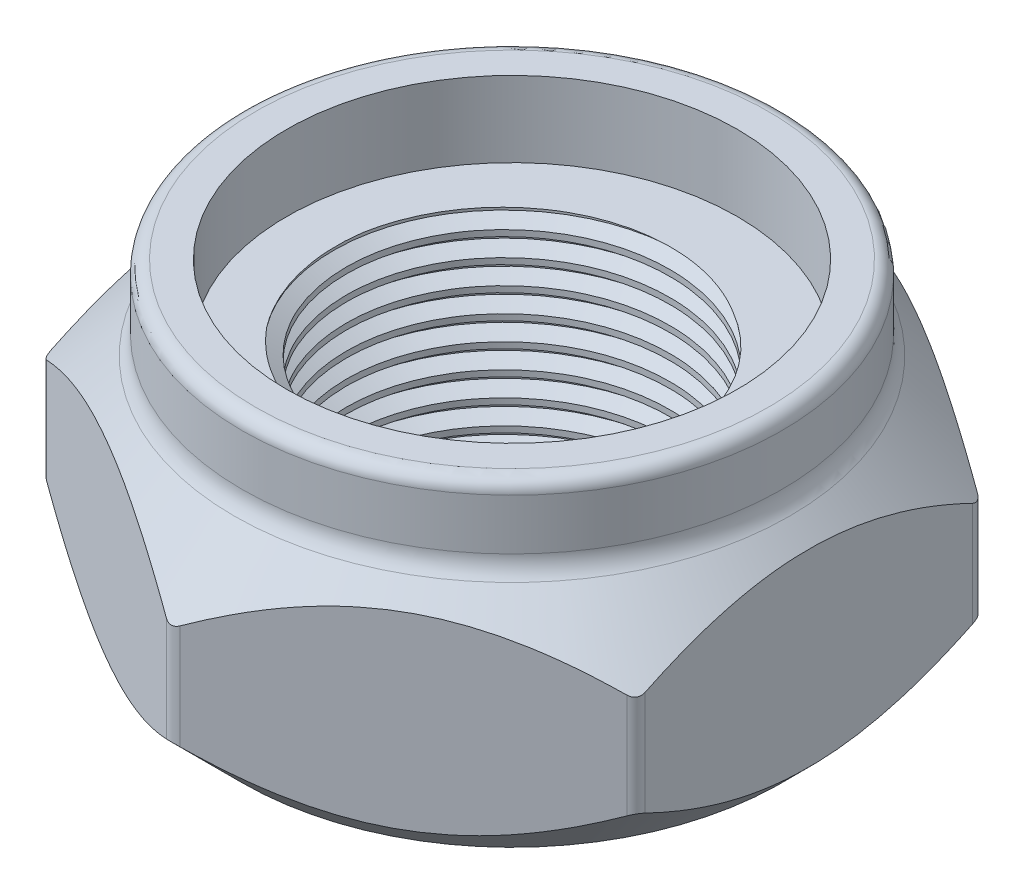
SolidWorks part; units mm, degrees
ref_plane "Front Plane" through (0, 0, 0) normal (0, 0, 1) x (1, 0, 0)
ref_plane "Top Plane" through (0, 0, 0) normal (0, 1, 0) x (1, 0, 0)
ref_plane "Right Plane" through (0, 0, 0) normal (1, 0, 0) x (0, 0, -1)
sketch "Sketch1" plane through (0, 0, 0) normal (0, 1, 0) x (1, 0, 0)
  line L1 (0, 6.3509) -> (-5.5, 3.1754)
  line L2 (-5.5, 3.1754) -> (-5.5, -3.1754)
  line L3 (-5.5, -3.1754) -> (0, -6.3509)
  line L4 (0, -6.3509) -> (5.5, -3.1754)
  line L5 (5.5, -3.1754) -> (5.5, 3.1754)
  line L6 (5.5, 3.1754) -> (0, 6.3509)
  circle A0 centre (0, 0) radius 5.5 construction
  dimension "D1" = 11
extrude "Boss-Extrude1" add sketch "Sketch1" along normal blind 6
sketch "Sketch2" plane through (0, 6, 0) normal (0, 1, 0) x (1, 0, 0)
  circle A0 centre (0, 0) radius 3
  dimension "D1" = 6
extrude "Cut-Extrude1" cut sketch "Sketch2" against normal blind 6
thread "Thread1" pitch 0.45 method cut profile "Thread Profile1" start angle 0, offset 0, length 0, pitch 0.45, diameter 6
ref_plane "Plane1" through (-3, 6, 0) normal (0, 0, 1) x (-1, 0, 0)
sketch "Thread Profile1" plane through (-3, 6, 0) normal (0, 0, 1) x (-1, 0, 0)
  line L0 (0, 0) -> (0, 0.45) construction
  line L1 (0, 0) -> (0.2436, 0.1406)
  line L2 (0.2436, 0.1406) -> (0.2436, 0.1969)
  line L3 (0.2436, 0.1969) -> (0, 0.3375)
  line L4 (0.2436, 0.1687) -> (0, 0.1687) construction
  line L11 (0, 0) -> (0, 0.3375)
  point P2 (0, 0)
  dimension "Pitch" = 0.45
  dimension "Profile_Angle" = 60
  dimension "Profile_Land" = 0.0562
  dimension "Profile_Height" = 0.2436
sketch "Sketch8" plane through (0, 6, 0) normal (0, 1, 0) x (1, 0, 0)
  circle A0 centre (0, 0) radius 7.8115
extrude "Cut-Extrude3" cut sketch "Sketch8" against normal blind 1.5 contours A0
sketch "Sketch9" plane through (0, 0, 0) normal (0, 0, 1) x (1, 0, 0)
  line L0 (0, -1.8255) -> (0, 6.4438) construction
  line L1 (-6.5, 3) -> (-6.5, 5.5)
  line L2 (-6.5, 5.5) -> (-4, 5.5)
  line L3 (-4, 5.5) -> (-6.5, 3)
  line L4 (-6.5, 1.5) -> (-6.5, -1)
  line L5 (-6.5, -1) -> (-4, -1)
  line L6 (-4, -1) -> (-6.5, 1.5)
  line L7 (-5.5, 4.5) -> (-5.5, 0) construction
  line L8 (-5.5, 4.5) -> (0, 4.5) construction
  line L9 (-5.5, 0) -> (0, 0) construction
  dimension "D1" = 1
  dimension "D2" = 1
  dimension "D3" = 1
  dimension "D4" = 1
  dimension "D5" = 2.5
  dimension "D6" = 2.5
  dimension "D7" = 2.5
  dimension "D8" = 2.5
revolve "Cut-Revolve3" cut sketch "Sketch9" angle 360 about L0 reverse direction yes
sketch "Sketch10" plane through (0, 4.5, 0) normal (0, 1, 0) x (1, 0, 0)
  circle A0 centre (0, 0) radius 5
  circle A1 centre (0, 0) radius 4.175
  dimension "D1" = 10
  dimension "D2" = 8.35
extrude "Boss-Extrude2" add sketch "Sketch10" along normal blind 1.4
fillet "Fillet1" radius 0.5 1 edges at (0, 4.5, 5)
fillet "Fillet2" radius 0.25 7 edges at (0, 2.25, -6.3509) (5.5, 2.25, -3.1754) (5.5, 2.25, 3.1754) (0, 2.25, 6.3509) (-5.5, 2.25, 3.1754) (-5.5, 2.25, -3.1754) (0, 5.9, 5)
